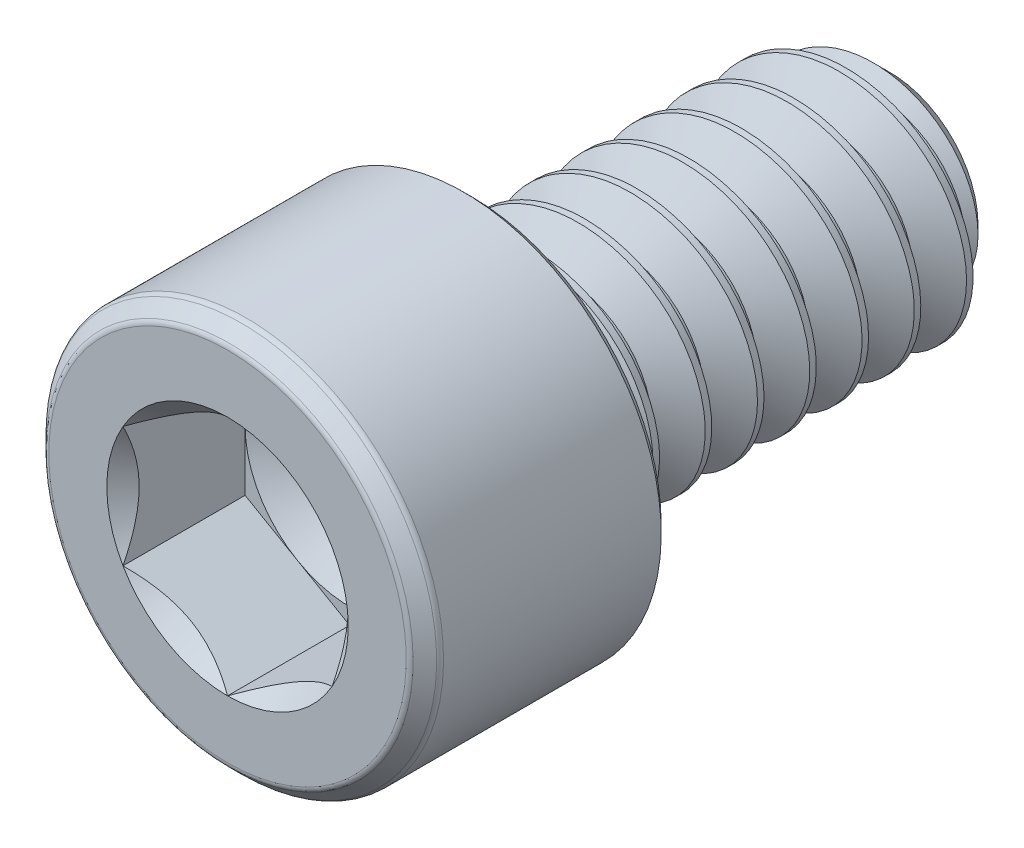
SolidWorks part; units mm, degrees
ref_plane "Front Plane" through (0, 0, 0) normal (0, 0, 1) x (1, 0, 0)
ref_plane "Top Plane" through (0, 0, 0) normal (0, 1, 0) x (1, 0, 0)
ref_plane "Right Plane" through (0, 0, 0) normal (1, 0, 0) x (0, 0, -1)
sketch "Sketch1" plane through (0, 0, 0) normal (1, 0, 0) x (0, 0, -1)
  line L0 (-2.5146, 0) -> (2.5146, 0) construction
  line L1 (-2.5146, 0) -> (-2.5146, 1.4986) construction
  line L2 (-2.5146, 1.4986) -> (-0.6604, 1.4986) construction
  line L3 (-0.6604, 1.4986) -> (-0.6604, 0.9271) construction
  line L4 (-0.6604, 0.9271) -> (2.2568, 0.9271) construction
  line L5 (2.4898, 0.9701) -> (2.6882, 0.6264) construction
  line L6 (2.6882, 0.6264) -> (2.8867, 0.9701) construction
  line L7 (2.8867, 0.9701) -> (2.4898, 0.9701) construction
  line L8 (2.2568, 0.9271) -> (2.5146, 0.6693) construction
  line L9 (2.5146, 0.6693) -> (2.5146, 0) construction
  line L10 (2.5146, 0.9271) -> (2.8619, 0.9271) construction
  line L11 (2.6882, 0.9701) -> (2.6882, 0.9271) construction
  line L12 (2.6882, 0.9271) -> (2.6882, 0.6693) construction
  line L13 (2.6882, 0.6693) -> (2.6882, 0.6264) construction
  line L14 (2.6634, 0.6693) -> (2.713, 0.6693) construction
  line L15 (2.5022, 0.9486) -> (2.8743, 0.9486) construction
  line L16 (2.713, 0.6693) -> (2.8743, 0.9486) construction
  line L17 (2.6634, 0.6693) -> (2.5022, 0.9486) construction
  line L18 (-2.5146, 0.7938) -> (-1.5875, 0.7938) construction
  line L19 (-1.5875, 0.7938) -> (-1.5875, 0) construction
  line L20 (1.1255, 0.9271) -> (1.1255, -0.9271) construction
  point P20 (2.6882, 0.9486)
  point P22 (1.1255, -0.9271)
  point P28 (1.1255, 0)
  point P29 (2.2568, -0.9271)
  point P30 (-1.124, 1.4986)
  point P31 (3.9751, 0)
  point P33 (-2.1209, 0)
  dimension "Length" = 3.175
  dimension "Head Height" = 1.8542
  dimension "D1" = 45
  dimension "Thread Pitch" = 0.3969
  dimension "D3" = 0.0496
  dimension "D4" = 1.3891
  dimension "D5" = 0.9271
  dimension "D2" = 1.3906
  dimension "Head Diameter" = 2.9972
  dimension "Drive Size" = 1.5875
  dimension "Screw Size Decimal Equivalent" = 1.8542
  dimension "D6" = 4.6355
  dimension "D7" = 4.6355
sketch "Sketch3" plane through (0, 0, 0) normal (1, 0, 0) x (0, 0, -1)
  line L0 (-2.5146, 1.357) -> (-2.5146, 0.7938)
  line L1 (-2.5146, 0.7938) -> (-1.5875, 0.7938)
  line L2 (-1.5875, 0.7938) -> (-1.5875, 0)
  line L3 (-1.5875, 0) -> (2.5146, 0)
  line L4 (2.5146, 0) -> (2.5146, 0.6693)
  line L5 (2.5146, 0.6693) -> (2.2568, 0.9271)
  line L6 (2.2568, 0.9271) -> (-0.5445, 0.9271)
  line L7 (-0.6604, 1.043) -> (-0.6604, 1.4387)
  line L8 (-0.7203, 1.4986) -> (-2.373, 1.4986)
  line L9 (-2.4992, 1.3941) -> (-2.4101, 1.4832)
  line L11 (-2.5146, 1.4986) -> (-0.6604, 1.4986) construction
  line L14 (-0.7203, 1.4986) -> (-0.6604, 1.4387)
  arc A0 (-2.4101, 1.4832) -> (-2.373, 1.4986) centre (-2.373, 1.4461) cw
  arc A1 (-2.4992, 1.3941) -> (-2.5146, 1.357) centre (-2.4621, 1.357) ccw
  arc A6 (-0.5445, 0.9271) -> (-0.6604, 1.043) centre (-0.5445, 1.043) cw
  point P25 (-2.5146, 1.3787)
  point P33 (-0.6604, 0.9271)
  dimension "D3" = 0.0525
  dimension "D10" = 0.1159
  dimension "D1" = 45
  dimension "D2" = 0.1199
  dimension "D7" = 45
  dimension "D8" = 0.0599
revolve "Revolve1" add sketch "Sketch3" angle 360 about L0
sketch "Sketch4" plane through (0, 0, 2.5146) normal (0, 0, 1) x (1, 0, 0)
  line L1 (0, 0.9165) -> (-0.7937, 0.4583)
  line L2 (-0.7937, 0.4583) -> (-0.7937, -0.4583)
  line L3 (-0.7937, -0.4583) -> (0, -0.9165)
  line L4 (0, -0.9165) -> (0.7937, -0.4583)
  line L5 (0.7937, -0.4583) -> (0.7937, 0.4583)
  line L6 (0.7937, 0.4583) -> (0, 0.9165)
  circle A0 centre (0, 0) radius 0.7937 construction
extrude "Cut-Extrude1" cut sketch "Sketch4" against normal up to vertex (0.9271 mm away) up to point (0, 0.7938, 1.5875)
sketch "Sketch5" plane through (0, 0, 2.5146) normal (0, 0, 1) x (1, 0, 0)
  circle A0 centre (0, 0) radius 0.9165
extrude "Cut-Extrude2" cut sketch "Sketch5" against normal up to next (0.9271 mm away) draft 45
sketch "Sketch10" plane through (0, 0, 1.5875) normal (0, 0, 1) x (1, 0, 0)
  line L0 (0.7937, 0.4583) -> (0.7937, -0.4583) construction
  circle A0 centre (0, 0) radius 0.7937
extrude "Cut-Extrude3" cut sketch "Sketch10" against normal through all draft 60
sketch "Sketch6" plane through (0, 0, -2.5146) normal (0, 0, -1) x (-1, 0, 0)
  circle A0 centre (0, 0) radius 0.9271 construction
  circle A1 centre (0, 0) radius 0.9271
curve "Helix/Spiral1" pitch 0.3969 height 3.5719 radius 0.9271 centre (0, 0, -2.5146) axis (0, 0, 1) start towards (0, 1, 0)
ref_plane "Plane1" through (0, 0, 0.5445) normal (0, 0, 1) x (1, 0, 0)
split "Split1" trim tools "Plane1" bodies to split 112 resulting bodies 118 119
sketch "Sketch7" plane through (0, 0, 0) normal (1, 0, 0) x (0, 0, -1)
  line L0 (2.6634, 0.6693) -> (2.713, 0.6693)
  line L8 (2.5022, 0.9486) -> (2.8743, 0.9486)
  line L9 (2.8743, 0.9486) -> (2.713, 0.6693)
  line L11 (2.6634, 0.6693) -> (2.5022, 0.9486)
sweep "Cut-Sweep1" cut profiles "Sketch7" path "Helix/Spiral1" align with end faces yes
sketch "Sketch11" plane through (0, 0, 0) normal (1, 0, 0) x (0, 0, -1)
  line L2 (-0.6604, 0.9271) -> (2.2568, 0.9271) construction
  line L4 (-0.5445, 0.9271) -> (0.3826, 0)
  line L5 (-2.5146, 0) -> (2.5146, 0) construction
  line L9 (-1.1292, 0.9271) -> (-1.1292, 0)
  line L10 (-1.1292, 0) -> (0.3826, 0)
  line L12 (-1.1292, 0.9271) -> (-0.5445, 0.9271)
  dimension "D1" = 45
revolve "Revolve2" add sketch "Sketch11" angle 360 about L0
equation "\"D3@Sketch1\" = \"Thread Pitch@Sketch1\" / 8"
equation "\"D4@Sketch1\" = \"Thread Pitch@Sketch1\" * 3.5"
equation "\"D3@Helix/Spiral1\"=\"Length@Sketch1\" +( \"Thread Pitch@Sketch1\")"
equation "\"D4@Helix/Spiral1\" = \"Thread Pitch@Sketch1\""
equation "\"D5@Sketch1\"=\"Head Height@Sketch1\"*0.5"
equation "\"D2@Sketch3\"=\"Head Diameter@Sketch1\" /25"
equation "\"D3@Sketch3\"=\"D2@Sketch3\"*0.4375"
equation "\"D2@Sketch1\"=\"Head Height@Sketch1\"*0.75"
equation "\"D8@Sketch3\"=\"D2@Sketch3\"*0.5"
equation "\"D10@Sketch3\"=\"Screw Size Decimal Equivalent@Sketch1\"*0.0625"
equation "\"D7@Sketch1\"=\"Screw Size Decimal Equivalent@Sketch1\"*2.5"
equation "\"D6@Sketch1\"=\"D7@Sketch1\""
equation "\"D3@Sketch1\"=\"Thread Pitch@Sketch1\"/8"
